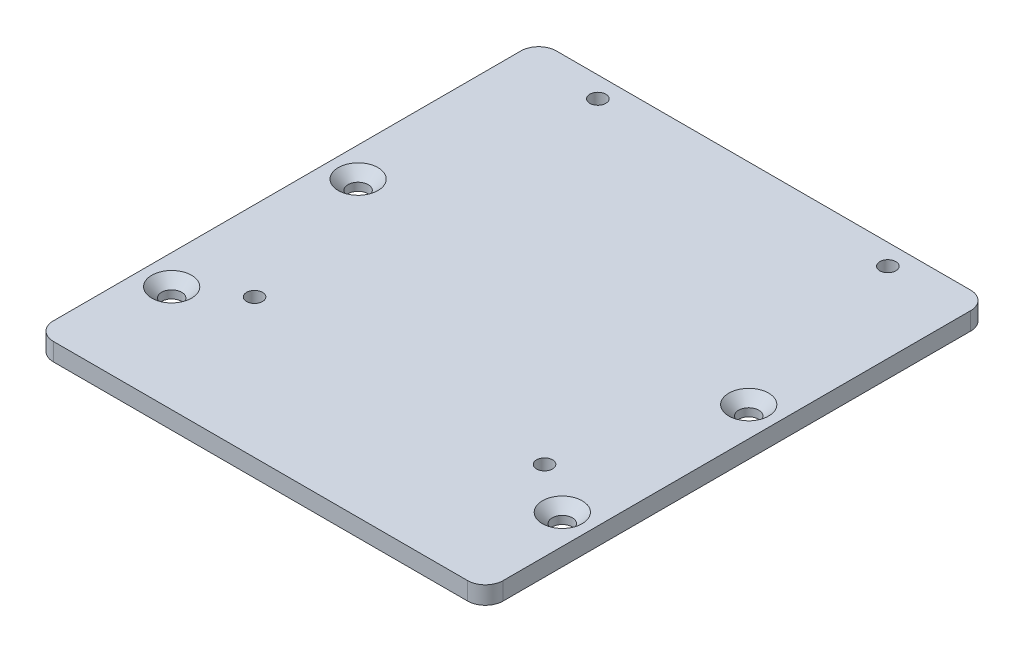
SolidWorks part; units mm, degrees
material "6061-T6 (SS)"
ref_plane "Front Plane" through (0, 0, 0) normal (0, 0, 1) x (1, 0, 0)
ref_plane "Top Plane" through (0, 0, 0) normal (0, 1, 0) x (1, 0, 0)
ref_plane "Right Plane" through (0, 0, 0) normal (1, 0, 0) x (0, 0, -1)
sketch "Sketch1" plane through (0, 0, 0) normal (0, 1, 0) x (1, 0, 0)
  line L0 (-33, 7) -> (-33, -24.5) construction
  line L1 (33, -24.5) -> (33, 7) construction
  line L2 (-33, 0) -> (33, 0) construction
  line L4 (38, -42.5) -> (-38, -42.5)
  line L5 (38, -42.5) -> (38, 42.5)
  line L6 (38, 42.5) -> (-38, 42.5)
  line L7 (-38, -42.5) -> (-38, 42.5)
  line L8 (38, -42.5) -> (-38, 42.5) construction
  line L9 (38, 42.5) -> (-38, -42.5) construction
  line L10 (24.5, -19) -> (-24.5, -19) construction
  line L11 (24.5, -19) -> (24.5, 39) construction
  line L12 (24.5, 39) -> (-24.5, 39) construction
  line L13 (-24.5, -19) -> (-24.5, 39) construction
  line L14 (24.5, -19) -> (-24.5, 39) construction
  line L15 (24.5, 39) -> (-24.5, -19) construction
  point P4 (0, 0)
  point P7 (0, 10)
  point P12 (0, 0)
  dimension "D1" = 31.5
  dimension "D2" = 7
  dimension "D3" = 85
  dimension "D4" = 76
  dimension "D5" = 49
  dimension "D6" = 58
  dimension "D7" = 3.5
  dimension "D8" = 5
extrude "Boss-Extrude1" add sketch "Sketch1" along normal blind 3
hole_wizard "M2.5 Clearance Hole1" positions "Sketch2" profile "Sketch3" hole size "M2.5" standard "ANSI Metric" end condition through all
sketch "Sketch2" plane through (0, 3, 0) normal (0, 1, 0) x (1, 0, 0)
  point P0 (-24.5, 39)
  point P3 (-24.5, -19)
  point P6 (24.5, -19)
  point P9 (24.5, 39)
sketch "Sketch3" plane through (-24.5, 3, -39) normal (1, 0, 0) x (0, 0, 1)
  line L0 (0, 0) -> (0, 3)
  line L1 (0, 3) -> (1.35, 3)
  line L2 (1.35, 3) -> (1.35, 0)
  line L5 (1.35, 0) -> (0, 0)
  line L11 (0, -6.35) -> (0, 107.95) construction
  dimension "Thru Hole Dia." = 2.7
  dimension "Thru Hole Depth" = 3
hole_wizard "CSK for M3 SFHCS1" positions "Sketch4" profile "Sketch5" countersink size "M3" standard "ANSI Metric" end condition through all
sketch "Sketch4" plane through (0, 3, 0) normal (0, 1, 0) x (1, 0, 0)
  point P0 (-33, -24.5)
  point P3 (-33, 7)
  point P6 (33, 7)
  point P9 (33, -24.5)
sketch "Sketch5" plane through (-33, 3, 24.5) normal (1, 0, 0) x (0, 0, 1)
  line L0 (0, 0) -> (0, 3)
  line L1 (0, 3) -> (1.7, 3)
  line L2 (1.7, 3) -> (1.7, 1.66)
  line L3 (1.7, 1.66) -> (3.36, 0)
  line L5 (3.36, 0) -> (0, 0)
  line L6 (-1.7, 1.66) -> (-3.36, 0) construction
  line L11 (0, -6.35) -> (0, 107.95) construction
  dimension "Thru Hole Dia." = 3.4
  dimension "Thru Hole Depth" = 3
  dimension "Near C'Sink Dia." = 6.72
  dimension "Near C'Sink Angle" = 90
fillet "Fillet1" radius 3 4 edges at (-38, 1.5, -42.5) (38, 1.5, -42.5) (38, 1.5, 42.5) (-38, 1.5, 42.5)
